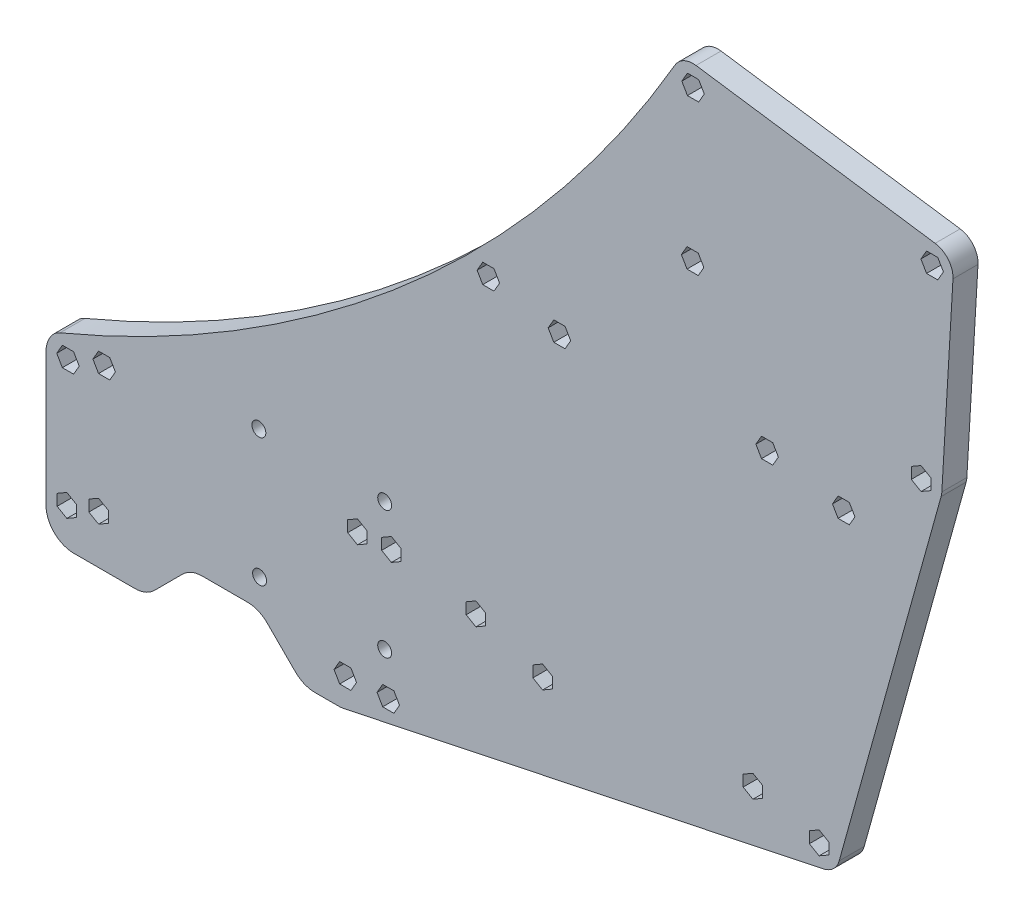
SolidWorks part; units mm, degrees
ref_plane "Front Plane" through (0, 0, 0) normal (0, 0, 1) x (1, 0, 0)
ref_plane "Top Plane" through (0, 0, 0) normal (0, 1, 0) x (1, 0, 0)
ref_plane "Right Plane" through (0, 0, 0) normal (1, 0, 0) x (0, 0, -1)
sketch "Model" plane through (0, 0, 0) normal (0, 0, 1) x (1, 0, 0)
  line L0 (-211.7059, 139.5585) -> (211.7058, 139.5585)
  line L1 (211.7058, 139.5585) -> (122.9838, -139.5584)
  line L2 (122.9838, -139.5584) -> (-211.7059, -139.5584)
  line L3 (-211.7059, -139.5584) -> (-211.7059, 139.5585)
  line L4 (-183.9889, -135.0098) -> (-175.7383, -135.0098)
  line L5 (-175.7383, -135.0098) -> (-175.7383, -139.5584)
  line L6 (-175.7383, -139.5584) -> (-183.9889, -139.5584)
  line L7 (-183.9889, -139.5584) -> (-183.9889, -135.0098)
  line L8 (5.1137, -131.3253) -> (16.7271, -131.3253)
  line L9 (16.7271, -131.3253) -> (16.7271, -139.5584)
  line L10 (16.7271, -139.5584) -> (5.1137, -139.5584)
  line L11 (5.1137, -139.5584) -> (5.1137, -131.3253)
  line L12 (-120.7856, -123.5542) -> (-97.2926, -123.5542)
  line L13 (-97.2926, -123.5542) -> (-97.2926, -126.7942)
  line L14 (-97.2926, -126.7942) -> (-120.7856, -126.7942)
  line L15 (-120.7856, -126.7942) -> (-120.7856, -123.5542)
  line L16 (-130.4136, -13.1631) -> (-127.7548, -13.1631)
  line L17 (-127.7548, -13.1631) -> (-127.7548, -110.9397)
  line L18 (-127.7548, -110.9397) -> (-130.4136, -110.9397)
  line L19 (-130.4136, -110.9397) -> (-130.4136, -13.1631)
  spline S0 degree 3 poles (121.2808, 104.4697) (121.2808, 103.8066) (121.0175, 103.1708) (120.5486, 102.7019) knots 0 0 0 0 1 1 1 1
  spline S1 degree 3 poles (120.5486, 102.7019) (120.0798, 102.2331) (119.4439, 101.9697) (118.7809, 101.9697) knots 0 0 0 0 1 1 1 1
  spline S2 degree 3 poles (118.7809, 101.9697) (117.4002, 101.9697) (116.2809, 103.089) (116.2809, 104.4697) knots 0 0 0 0 1 1 1 1
  spline S3 degree 3 poles (116.2809, 104.4697) (116.2809, 105.8504) (117.4002, 106.9696) (118.7809, 106.9696) knots 0 0 0 0 1 1 1 1
  spline S4 degree 3 poles (118.7809, 106.9696) (119.4439, 106.9696) (120.0798, 106.7062) (120.5486, 106.2374) knots 0 0 0 0 1 1 1 1
  spline S5 degree 3 poles (120.5486, 106.2374) (121.0175, 105.7686) (121.2808, 105.1327) (121.2808, 104.4697) knots 0 0 0 0 1 1 1 1
  spline S6 degree 3 poles (117.2766, 36.0936) (117.2766, 34.7129) (116.1574, 33.5937) (114.7767, 33.5937) knots 0 0 0 0 1 1 1 1
  spline S7 degree 3 poles (114.7767, 33.5937) (113.396, 33.5937) (112.2767, 34.7129) (112.2767, 36.0936) knots 0 0 0 0 1 1 1 1
  spline S8 degree 3 poles (112.2767, 36.0936) (112.2767, 37.4743) (113.396, 38.5936) (114.7767, 38.5936) knots 0 0 0 0 1 1 1 1
  spline S9 degree 3 poles (114.7767, 38.5936) (116.1574, 38.5936) (117.2766, 37.4743) (117.2766, 36.0936) knots 0 0 0 0 1 1 1 1
  spline S10 degree 3 poles (61.9275, 17.0977) (61.9275, 15.717) (60.8082, 14.5977) (59.4275, 14.5977) knots 0 0 0 0 1 1 1 1
  spline S11 degree 3 poles (59.4275, 14.5977) (58.0468, 14.5977) (56.9275, 15.717) (56.9275, 17.0977) knots 0 0 0 0 1 1 1 1
  spline S12 degree 3 poles (56.9275, 17.0977) (56.9275, 18.4784) (58.0468, 19.5976) (59.4275, 19.5976) knots 0 0 0 0 1 1 1 1
  spline S13 degree 3 poles (59.4275, 19.5976) (60.8082, 19.5976) (61.9275, 18.4784) (61.9275, 17.0977) knots 0 0 0 0 1 1 1 1
  spline S14 degree 3 poles (35.1266, 62.7496) (35.1266, 61.3689) (34.0074, 60.2496) (32.6267, 60.2496) knots 0 0 0 0 1 1 1 1
  spline S15 degree 3 poles (32.6267, 60.2496) (31.246, 60.2496) (30.1267, 61.3689) (30.1267, 62.7496) knots 0 0 0 0 1 1 1 1
  spline S16 degree 3 poles (30.1267, 62.7496) (30.1267, 64.1303) (31.246, 65.2496) (32.6267, 65.2496) knots 0 0 0 0 1 1 1 1
  spline S17 degree 3 poles (32.6267, 65.2496) (34.0074, 65.2496) (35.1266, 64.1303) (35.1266, 62.7496) knots 0 0 0 0 1 1 1 1
  spline S18 degree 3 poles (35.2798, 116.8664) (35.2798, 115.4857) (34.1605, 114.3664) (32.7798, 114.3664) knots 0 0 0 0 1 1 1 1
  spline S19 degree 3 poles (32.7798, 114.3664) (31.3991, 114.3664) (30.2798, 115.4857) (30.2798, 116.8664) knots 0 0 0 0 1 1 1 1
  spline S20 degree 3 poles (30.2798, 116.8664) (30.2798, 117.5294) (30.5432, 118.1653) (31.0121, 118.6341) knots 0 0 0 0 1 1 1 1
  spline S21 degree 3 poles (31.0121, 118.6341) (31.4809, 119.103) (32.1168, 119.3664) (32.7798, 119.3664) knots 0 0 0 0 1 1 1 1
  spline S22 degree 3 poles (32.7798, 119.3664) (33.4428, 119.3664) (34.0787, 119.103) (34.5475, 118.6341) knots 0 0 0 0 1 1 1 1
  spline S23 degree 3 poles (34.5475, 118.6341) (35.0164, 118.1653) (35.2798, 117.5294) (35.2798, 116.8664) knots 0 0 0 0 1 1 1 1
  spline S24 degree 3 poles (56.804, -89.9943) (56.804, -91.375) (55.6847, -92.4943) (54.304, -92.4943) knots 0 0 0 0 1 1 1 1
  spline S25 degree 3 poles (54.304, -92.4943) (52.9233, -92.4943) (51.804, -91.375) (51.804, -89.9943) knots 0 0 0 0 1 1 1 1
  spline S26 degree 3 poles (51.804, -89.9943) (51.804, -88.6136) (52.9233, -87.4943) (54.304, -87.4943) knots 0 0 0 0 1 1 1 1
  spline S27 degree 3 poles (54.304, -87.4943) (55.6847, -87.4943) (56.804, -88.6136) (56.804, -89.9943) knots 0 0 0 0 1 1 1 1
  spline S28 degree 3 poles (80.6115, -95.7304) (80.6115, -97.1111) (79.4922, -98.2304) (78.1115, -98.2304) knots 0 0 0 0 1 1 1 1
  spline S29 degree 3 poles (78.1115, -98.2304) (76.7308, -98.2304) (75.6115, -97.1111) (75.6115, -95.7304) knots 0 0 0 0 1 1 1 1
  spline S30 degree 3 poles (75.6115, -95.7304) (75.6115, -94.3497) (76.7308, -93.2304) (78.1115, -93.2304) knots 0 0 0 0 1 1 1 1
  spline S31 degree 3 poles (78.1115, -93.2304) (79.4922, -93.2304) (80.6115, -94.3497) (80.6115, -95.7304) knots 0 0 0 0 1 1 1 1
  spline S32 degree 3 poles (-189.541, -80.3042) (-189.541, -81.6849) (-190.6603, -82.8042) (-192.041, -82.8042) knots 0 0 0 0 1 1 1 1
  spline S33 degree 3 poles (-192.041, -82.8042) (-193.4217, -82.8042) (-194.5409, -81.6849) (-194.5409, -80.3042) knots 0 0 0 0 1 1 1 1
  spline S34 degree 3 poles (-194.5409, -80.3042) (-194.5409, -78.9235) (-193.4217, -77.8043) (-192.041, -77.8043) knots 0 0 0 0 1 1 1 1
  spline S35 degree 3 poles (-192.041, -77.8043) (-190.6603, -77.8043) (-189.541, -78.9235) (-189.541, -80.3042) knots 0 0 0 0 1 1 1 1
  spline S36 degree 3 poles (-85.4284, -81.8636) (-85.4284, -82.5266) (-85.6918, -83.1625) (-86.1606, -83.6313) knots 0 0 0 0 1 1 1 1
  spline S37 degree 3 poles (-86.1606, -83.6313) (-86.6295, -84.1001) (-87.2654, -84.3635) (-87.9284, -84.3635) knots 0 0 0 0 1 1 1 1
  spline S38 degree 3 poles (-87.9284, -84.3635) (-88.5914, -84.3635) (-89.2273, -84.1001) (-89.6961, -83.6313) knots 0 0 0 0 1 1 1 1
  spline S39 degree 3 poles (-89.6961, -83.6313) (-90.165, -83.1625) (-90.4284, -82.5266) (-90.4284, -81.8636) knots 0 0 0 0 1 1 1 1
  spline S40 degree 3 poles (-90.4284, -81.8636) (-90.4284, -80.4829) (-89.3091, -79.3636) (-87.9284, -79.3636) knots 0 0 0 0 1 1 1 1
  spline S41 degree 3 poles (-87.9284, -79.3636) (-86.5477, -79.3636) (-85.4284, -80.4829) (-85.4284, -81.8636) knots 0 0 0 0 1 1 1 1
  spline S42 degree 3 poles (-73.2184, -81.251) (-73.2184, -82.6317) (-74.3377, -83.7509) (-75.7183, -83.7509) knots 0 0 0 0 1 1 1 1
  spline S43 degree 3 poles (-75.7183, -83.7509) (-76.3814, -83.7509) (-77.0173, -83.4875) (-77.4861, -83.0187) knots 0 0 0 0 1 1 1 1
  spline S44 degree 3 poles (-77.4861, -83.0187) (-77.9549, -82.5499) (-78.2183, -81.914) (-78.2183, -81.251) knots 0 0 0 0 1 1 1 1
  spline S45 degree 3 poles (-78.2183, -81.251) (-78.2183, -80.5879) (-77.9549, -79.9521) (-77.4861, -79.4832) knots 0 0 0 0 1 1 1 1
  spline S46 degree 3 poles (-77.4861, -79.4832) (-77.0173, -79.0144) (-76.3814, -78.751) (-75.7183, -78.751) knots 0 0 0 0 1 1 1 1
  spline S47 degree 3 poles (-75.7183, -78.751) (-74.3377, -78.751) (-73.2184, -79.8703) (-73.2184, -81.251) knots 0 0 0 0 1 1 1 1
  spline S48 degree 3 poles (-42.8255, -86.1238) (-42.8255, -86.7869) (-43.0889, -87.4228) (-43.5578, -87.8916) knots 0 0 0 0 1 1 1 1
  spline S49 degree 3 poles (-43.5578, -87.8916) (-44.0266, -88.3604) (-44.6625, -88.6238) (-45.3255, -88.6238) knots 0 0 0 0 1 1 1 1
  spline S50 degree 3 poles (-45.3255, -88.6238) (-45.9885, -88.6238) (-46.6244, -88.3604) (-47.0932, -87.8916) knots 0 0 0 0 1 1 1 1
  spline S51 degree 3 poles (-47.0932, -87.8916) (-47.5621, -87.4228) (-47.8255, -86.7869) (-47.8255, -86.1238) knots 0 0 0 0 1 1 1 1
  spline S52 degree 3 poles (-47.8255, -86.1238) (-47.8255, -84.7432) (-46.7062, -83.6239) (-45.3255, -83.6239) knots 0 0 0 0 1 1 1 1
  spline S53 degree 3 poles (-45.3255, -83.6239) (-43.9448, -83.6239) (-42.8255, -84.7432) (-42.8255, -86.1238) knots 0 0 0 0 1 1 1 1
  spline S54 degree 3 poles (-18.8231, -93.7812) (-18.8231, -95.1619) (-19.9424, -96.2812) (-21.3231, -96.2812) knots 0 0 0 0 1 1 1 1
  spline S55 degree 3 poles (-21.3231, -96.2812) (-22.7038, -96.2812) (-23.823, -95.1619) (-23.823, -93.7812) knots 0 0 0 0 1 1 1 1
  spline S56 degree 3 poles (-23.823, -93.7812) (-23.823, -92.4005) (-22.7038, -91.2813) (-21.3231, -91.2813) knots 0 0 0 0 1 1 1 1
  spline S57 degree 3 poles (-21.3231, -91.2813) (-19.9424, -91.2813) (-18.8231, -92.4005) (-18.8231, -93.7812) knots 0 0 0 0 1 1 1 1
  spline S58 degree 3 poles (-38.3425, 21.163) (-38.3425, 19.7824) (-39.4618, 18.6631) (-40.8425, 18.6631) knots 0 0 0 0 1 1 1 1
  spline S59 degree 3 poles (-40.8425, 18.6631) (-42.2231, 18.6631) (-43.3424, 19.7824) (-43.3424, 21.163) knots 0 0 0 0 1 1 1 1
  spline S60 degree 3 poles (-43.3424, 21.163) (-43.3424, 22.5437) (-42.2231, 23.663) (-40.8425, 23.663) knots 0 0 0 0 1 1 1 1
  spline S61 degree 3 poles (-40.8425, 23.663) (-39.4618, 23.663) (-38.3425, 22.5437) (-38.3425, 21.163) knots 0 0 0 0 1 1 1 1
  spline S62 degree 3 poles (-12.7807, 15.9839) (-12.7807, 14.6032) (-13.9, 13.4839) (-15.2807, 13.4839) knots 0 0 0 0 1 1 1 1
  spline S63 degree 3 poles (-15.2807, 13.4839) (-16.6614, 13.4839) (-17.7807, 14.6032) (-17.7807, 15.9839) knots 0 0 0 0 1 1 1 1
  spline S64 degree 3 poles (-17.7807, 15.9839) (-17.7807, 17.3646) (-16.6614, 18.4838) (-15.2807, 18.4838) knots 0 0 0 0 1 1 1 1
  spline S65 degree 3 poles (-15.2807, 18.4838) (-13.9, 18.4838) (-12.7807, 17.3646) (-12.7807, 15.9839) knots 0 0 0 0 1 1 1 1
  spline S66 degree 3 poles (-176.5282, -75.6233) (-176.5282, -76.2863) (-176.7916, -76.9222) (-177.2604, -77.391) knots 0 0 0 0 1 1 1 1
  spline S67 degree 3 poles (-177.2604, -77.391) (-177.7293, -77.8599) (-178.3651, -78.1233) (-179.0282, -78.1233) knots 0 0 0 0 1 1 1 1
  spline S68 degree 3 poles (-179.0282, -78.1233) (-179.6912, -78.1233) (-180.3271, -77.8599) (-180.7959, -77.391) knots 0 0 0 0 1 1 1 1
  spline S69 degree 3 poles (-180.7959, -77.391) (-181.2647, -76.9222) (-181.5281, -76.2863) (-181.5281, -75.6233) knots 0 0 0 0 1 1 1 1
  spline S70 degree 3 poles (-181.5281, -75.6233) (-181.5281, -74.2426) (-180.4089, -73.1233) (-179.0282, -73.1233) knots 0 0 0 0 1 1 1 1
  spline S71 degree 3 poles (-179.0282, -73.1233) (-177.6475, -73.1233) (-176.5282, -74.2426) (-176.5282, -75.6233) knots 0 0 0 0 1 1 1 1
  spline S72 degree 3 poles (-189.9448, -125.9005) (-189.9448, -127.2812) (-191.064, -128.4004) (-192.4447, -128.4004) knots 0 0 0 0 1 1 1 1
  spline S73 degree 3 poles (-192.4447, -128.4004) (-193.8254, -128.4004) (-194.9447, -127.2812) (-194.9447, -125.9005) knots 0 0 0 0 1 1 1 1
  spline S74 degree 3 poles (-194.9447, -125.9005) (-194.9447, -124.5198) (-193.8254, -123.4005) (-192.4447, -123.4005) knots 0 0 0 0 1 1 1 1
  spline S75 degree 3 poles (-192.4447, -123.4005) (-191.064, -123.4005) (-189.9448, -124.5198) (-189.9448, -125.9005) knots 0 0 0 0 1 1 1 1
  spline S76 degree 3 poles (-178.5283, -121.9882) (-178.5283, -123.3689) (-179.6475, -124.4882) (-181.0282, -124.4882) knots 0 0 0 0 1 1 1 1
  spline S77 degree 3 poles (-181.0282, -124.4882) (-181.6913, -124.4882) (-182.3271, -124.2248) (-182.796, -123.756) knots 0 0 0 0 1 1 1 1
  spline S78 degree 3 poles (-182.796, -123.756) (-183.2648, -123.2871) (-183.5282, -122.6513) (-183.5282, -121.9882) knots 0 0 0 0 1 1 1 1
  spline S79 degree 3 poles (-183.5282, -121.9882) (-183.5282, -121.3252) (-183.2648, -120.6893) (-182.796, -120.2205) knots 0 0 0 0 1 1 1 1
  spline S80 degree 3 poles (-182.796, -120.2205) (-182.3271, -119.7516) (-181.6913, -119.4882) (-181.0282, -119.4882) knots 0 0 0 0 1 1 1 1
  spline S81 degree 3 poles (-181.0282, -119.4882) (-180.3652, -119.4882) (-179.7293, -119.7516) (-179.2605, -120.2205) knots 0 0 0 0 1 1 1 1
  spline S82 degree 3 poles (-179.2605, -120.2205) (-178.7917, -120.6893) (-178.5283, -121.3252) (-178.5283, -121.9882) knots 0 0 0 0 1 1 1 1
  spline S83 degree 3 poles (-74.3322, -128.3369) (-74.3322, -129.7176) (-75.4514, -130.8369) (-76.8321, -130.8369) knots 0 0 0 0 1 1 1 1
  spline S84 degree 3 poles (-76.8321, -130.8369) (-77.4952, -130.8369) (-78.1311, -130.5735) (-78.5999, -130.1046) knots 0 0 0 0 1 1 1 1
  spline S85 degree 3 poles (-78.5999, -130.1046) (-79.0687, -129.6358) (-79.3321, -128.9999) (-79.3321, -128.3369) knots 0 0 0 0 1 1 1 1
  spline S86 degree 3 poles (-79.3321, -128.3369) (-79.3321, -127.6739) (-79.0687, -127.038) (-78.5999, -126.5692) knots 0 0 0 0 1 1 1 1
  spline S87 degree 3 poles (-78.5999, -126.5692) (-78.1311, -126.1003) (-77.4952, -125.8369) (-76.8321, -125.8369) knots 0 0 0 0 1 1 1 1
  spline S88 degree 3 poles (-76.8321, -125.8369) (-75.4514, -125.8369) (-74.3322, -126.9562) (-74.3322, -128.3369) knots 0 0 0 0 1 1 1 1
  spline S89 degree 3 poles (-89.8001, -128.9495) (-89.8001, -129.6125) (-90.0635, -130.2484) (-90.5323, -130.7172) knots 0 0 0 0 1 1 1 1
  spline S90 degree 3 poles (-90.5323, -130.7172) (-91.0012, -131.1861) (-91.637, -131.4494) (-92.3001, -131.4494) knots 0 0 0 0 1 1 1 1
  spline S91 degree 3 poles (-92.3001, -131.4494) (-93.6808, -131.4494) (-94.8, -130.3302) (-94.8, -128.9495) knots 0 0 0 0 1 1 1 1
  spline S92 degree 3 poles (-94.8, -128.9495) (-94.8, -127.5688) (-93.6808, -126.4495) (-92.3001, -126.4495) knots 0 0 0 0 1 1 1 1
  spline S93 degree 3 poles (-92.3001, -126.4495) (-91.637, -126.4495) (-91.0012, -126.7129) (-90.5323, -127.1817) knots 0 0 0 0 1 1 1 1
  spline S94 degree 3 poles (-90.5323, -127.1817) (-90.0635, -127.6506) (-89.8001, -128.2864) (-89.8001, -128.9495) knots 0 0 0 0 1 1 1 1
  spline S95 degree 3 poles (89.4662, 12.2666) (89.4662, 10.8859) (88.3469, 9.7666) (86.9662, 9.7666) knots 0 0 0 0 1 1 1 1
  spline S96 degree 3 poles (86.9662, 9.7666) (85.5855, 9.7666) (84.4663, 10.8859) (84.4663, 12.2666) knots 0 0 0 0 1 1 1 1
  spline S97 degree 3 poles (84.4663, 12.2666) (84.4663, 13.6472) (85.5855, 14.7665) (86.9662, 14.7665) knots 0 0 0 0 1 1 1 1
  spline S98 degree 3 poles (86.9662, 14.7665) (88.3469, 14.7665) (89.4662, 13.6472) (89.4662, 12.2666) knots 0 0 0 0 1 1 1 1
sketch "Sketch2" plane through (0, 0, 0) normal (0, 0, 1) x (1, 0, 0)
  line L0 (-211.7059, -139.5584) -> (122.9838, -139.5584)
  line L18 (-211.7059, -139.5584) -> (-211.7059, 139.5585)
  line L19 (-211.7059, 139.5585) -> (211.7058, 139.5585)
  line L20 (211.7058, 139.5585) -> (122.9838, -139.5584)
  circle A0 centre (-192.4447, -125.9005) radius 2.5
  circle A1 centre (-181.0282, -121.9882) radius 2.5
  circle A2 centre (-192.041, -80.3042) radius 2.5
  circle A3 centre (-179.0282, -75.6233) radius 2.5
  circle A4 centre (-92.3001, -128.9495) radius 2.5
  circle A5 centre (-76.8321, -128.3369) radius 2.5
  circle A6 centre (-87.9284, -81.8636) radius 2.5
  circle A7 centre (-75.7183, -81.251) radius 2.5
  circle A8 centre (-45.3255, -86.1239) radius 2.5
  circle A9 centre (-21.3231, -93.7812) radius 2.5
  circle A10 centre (54.304, -89.9943) radius 2.5
  circle A11 centre (78.1115, -95.7304) radius 2.5
  circle A12 centre (114.7767, 36.0936) radius 2.5
  circle A13 centre (86.9662, 12.2666) radius 2.5
  circle A14 centre (59.4275, 17.0977) radius 2.5
  circle A15 centre (-40.8425, 21.163) radius 2.5
  circle A16 centre (-15.2807, 15.9839) radius 2.5
  circle A17 centre (32.6267, 62.7496) radius 2.5
  circle A18 centre (118.7809, 104.4697) radius 2.5
  circle A19 centre (32.7798, 116.8664) radius 2.5
extrude "Boss-Extrude1" add sketch "Sketch2" along normal blind 9
sketch "Sketch3" plane through (0, 0, 9) normal (0, 0, 1) x (1, 0, 0)
  line L0 (73.706, -139.5584) -> (151.3388, 139.5585)
  line L1 (-211.7059, -139.5584) -> (122.9838, -139.5584) construction
  line L2 (-211.7059, 139.5585) -> (211.7058, 139.5585) construction
  line L3 (-199.9447, 139.5585) -> (-199.9447, -139.5584)
  line L4 (-211.7059, -87.5749) -> (47.2794, 139.5585)
  line L5 (-211.7059, -139.5584) -> (-211.7059, 139.5585) construction
  line L6 (-211.7059, 124.3664) -> (206.8768, 124.3664)
  line L7 (211.7058, 139.5585) -> (122.9838, -139.5584) construction
  line L9 (211.7058, 139.5585) -> (-211.7059, 139.5585)
  line L10 (211.7058, 139.5585) -> (211.7058, -139.5584)
  line L11 (211.7058, -139.5584) -> (-211.7059, -139.5584)
  line L12 (-211.7059, 139.5585) -> (-211.7059, -139.5584)
  circle A0 centre (114.7767, 36.0936) radius 7.5
  circle A1 centre (78.1115, -95.7304) radius 7.5
  circle A2 centre (-192.4447, -125.9005) radius 7.5
  circle A3 centre (-192.041, -80.3042) radius 7.5
  circle A4 centre (32.7798, 116.8664) radius 7.5
  circle A5 centre (114.7767, 36.0936) radius 2.5 construction
  circle A6 centre (118.7809, 104.4697) radius 7.5
  line M29 (122.9838, -139.5584) -> (211.7058, 139.5585)
  line M30 (211.7058, 139.5585) -> (-211.7059, 139.5585)
  line M31 (-211.7059, 139.5585) -> (-211.7059, -139.5584)
  line M32 (-211.7059, -139.5584) -> (122.9838, -139.5584)
  dimension "D1" = 15
extrude "Cut-Extrude1" cut sketch "Sketch3" against normal blind 10 contours L6 L4 L3 M31 | L4 L3 M31 M32 | L6 L0 M32 M29 | L6 L3 L4 | L6 L3 M31 M30 | L3 L6 L4 M30 | L4 L6 L0 M30 | L0 L6 M29 M30 | L12 L11 L10 L9
sketch "Sketch4" plane through (0, 0, 9) normal (0, 0, 1) x (1, 0, 0)
  line L5 (-163.8851, -139.5584) -> (-147.8809, -123.5542)
  line L6 (-199.9447, -139.5584) -> (73.706, -139.5584) construction
  line L7 (-147.8809, -123.5542) -> (-123.3337, -123.5542)
  line L8 (-123.3337, -123.5542) -> (-107.3295, -139.5584)
  line L9 (-107.3295, -139.5584) -> (-163.8851, -139.5584)
  line L10 (-155.883, -131.5563) -> (-115.3316, -131.5563) construction
  line L11 (-135.6073, -123.5542) -> (-135.6073, -131.5563) construction
  line L12 (-128.1309, -123.5542) -> (-73.1309, -123.5542) construction
  line L13 (-147.8809, -91.0542) -> (-123.3337, -91.0542) construction
  line L14 (-147.8809, -85.5542) -> (-147.8809, -96.5542) construction
  line L15 (-123.3337, -72.156) -> (-123.3337, -109.9525) construction
  line L16 (-135.6073, -123.5542) -> (-135.6073, -91.0542) construction
  line L17 (-147.8809, -117.5859) -> (-147.8809, -123.5542) construction
  dimension "D1" = 45
extrude "Cut-Extrude2" cut sketch "Sketch4" against normal through all
sketch "Sketch5" plane through (0, 0, 9) normal (0, 0, 1) x (1, 0, 0)
  line L0 (-120.6309, -113.5542) -> (-125.6309, -113.5542) construction
  line L1 (-120.6309, -117.5542) -> (-120.6309, -109.5542) construction
  line L3 (-123.3809, -117.5859) -> (-123.3809, -64.5226) construction
  line L4 (-75.6309, -67.5542) -> (-80.6309, -67.5542) construction
  line L5 (-75.6309, -72.0542) -> (-75.6309, -63.0542) construction
  line L6 (-80.6309, -63.0542) -> (-80.6309, -72.0542) construction
  line L7 (-78.1309, -67.5542) -> (-123.3809, -67.5542) construction
  line L8 (-78.1309, -113.5542) -> (-78.1309, -67.5542) construction
  line L9 (-123.1309, -113.5542) -> (-78.1309, -113.5542) construction
  circle A0 centre (-123.1309, -113.5542) radius 2.5
  circle A1 centre (-78.1309, -113.5542) radius 2.5
  circle A2 centre (-123.3809, -67.5542) radius 2.5
  circle A3 centre (-78.1309, -67.5542) radius 2.5
  dimension "D1" = 5
extrude "Cut-Extrude3" cut sketch "Sketch5" against normal through all
sketch "Sketch6" plane through (0, 0, 9) normal (0, 0, 1) x (1, 0, 0)
  line L0 (-199.9447, -77.2602) -> (-199.9447, -139.5584) construction
  line L1 (-194.9336, -73.3845) -> (-199.9447, -73.3845)
  line L2 (-199.9447, -139.5584) -> (147.1133, -139.5584)
  line L3 (-199.9447, -139.5584) -> (-199.9447, 124.3664)
  line L4 (-199.9447, 124.3664) -> (147.1133, 124.3664)
  line L5 (147.1133, -139.5584) -> (147.1133, 124.3664)
  line L6 (26.2967, 120.6372) -> (26.2967, 124.3664)
  line L7 (33.8498, 124.2897) -> (119.8509, 111.8929)
  line L8 (126.2681, 104.0312) -> (122.2638, 35.6552)
  line L9 (122.2638, 35.6552) -> (147.1133, 35.6552)
  line L10 (79.656, -103.0696) -> (-93.736, -139.5584)
  line L11 (79.656, -103.0696) -> (147.1133, -103.0696)
  circle A0 centre (-192.041, -80.3042) radius 7.5
  circle A1 centre (-40.8425, 21.163) radius 7.5
  circle A3 centre (114.7767, 36.0936) radius 7.5
  circle A4 centre (32.7798, 116.8664) radius 7.5
  circle A5 centre (118.7809, 104.4697) radius 7.5
  circle A6 centre (78.1115, -95.7304) radius 7.5
  circle A7 centre (-76.8321, -128.3369) radius 7.5
  circle A8 centre (-192.4447, -125.9005) radius 7.5
  circle A9 centre (-179.0282, -75.6233) radius 7.5
  arc A10 (-194.9336, -73.3845) -> (26.2967, 120.6372) centre (-373.1679, 352.9825) ccw
  line M19 (73.706, -139.5584) -> (147.1133, 124.3664)
  line M20 (147.1133, 124.3664) -> (29.9569, 124.3664)
  line M21 (29.9569, 124.3664) -> (-199.9447, -77.2602)
extrude "Cut-Extrude5" cut sketch "Sketch6" against normal blind 10 contours L1 A10 L6 M21 | L9 L5 M19 | L11 L10 L2 M19 | A6 L11 M19 | A0 L1 M21 | L6 L4 M21 | A4 L6 M21 | A4 L4 M21 | A5 L8 L9 A4 L7 M19 M20 | A3 L9 M19
fillet "Fillet1" radius 10 7 edges at (-199.9447, -77.2602, 4.5) (-163.8851, -139.5584, 4.5) (-147.8809, -123.5542, 4.5) (-123.3337, -123.5542, 4.5) (-107.3295, -139.5584, 4.5) (-93.736, -139.5584, 4.5) (-199.9447, -139.5584, 4.5)
sketch "Sketch7" plane through (0, 0, 0) normal (0, 0, 1) x (1, 0, 0)
  line L1 (-190.0202, -83.8042) -> (-187.9995, -80.3042)
  line L2 (-187.9995, -80.3042) -> (-190.0202, -76.8042)
  line L3 (-190.0202, -76.8042) -> (-194.0617, -76.8042)
  line L4 (-194.0617, -76.8042) -> (-196.0824, -80.3042)
  line L5 (-196.0824, -80.3042) -> (-194.0617, -83.8042)
  line L6 (-194.0617, -83.8042) -> (-190.0202, -83.8042)
  line L7 (-181.0489, -79.1233) -> (-177.0074, -79.1233)
  line L8 (-177.0074, -79.1233) -> (-174.9867, -75.6233)
  line L9 (-174.9867, -75.6233) -> (-177.0074, -72.1233)
  line L10 (-177.0074, -72.1233) -> (-181.0489, -72.1233)
  line L11 (-181.0489, -72.1233) -> (-183.0696, -75.6233)
  line L12 (-183.0696, -75.6233) -> (-181.0489, -79.1233)
  line L13 (-192.4447, -129.9419) -> (-188.9447, -127.9212)
  line L14 (-188.9447, -127.9212) -> (-188.9447, -123.8798)
  line L15 (-188.9447, -123.8798) -> (-192.4447, -121.859)
  line L16 (-192.4447, -121.859) -> (-195.9447, -123.8798)
  line L17 (-195.9447, -123.8798) -> (-195.9447, -127.9212)
  line L18 (-195.9447, -127.9212) -> (-192.4447, -129.9419)
  line L19 (-177.5282, -124.0089) -> (-177.5282, -119.9675)
  line L20 (-177.5282, -119.9675) -> (-181.0282, -117.9468)
  line L21 (-181.0282, -117.9468) -> (-184.5282, -119.9675)
  line L22 (-184.5282, -119.9675) -> (-184.5282, -124.0089)
  line L23 (-184.5282, -124.0089) -> (-181.0282, -126.0297)
  line L24 (-181.0282, -126.0297) -> (-177.5282, -124.0089)
  line L25 (-96.3415, -128.9495) -> (-94.3208, -132.4495)
  line L26 (-94.3208, -132.4495) -> (-90.2793, -132.4495)
  line L27 (-90.2793, -132.4495) -> (-88.2586, -128.9495)
  line L28 (-88.2586, -128.9495) -> (-90.2793, -125.4495)
  line L29 (-90.2793, -125.4495) -> (-94.3208, -125.4495)
  line L30 (-94.3208, -125.4495) -> (-96.3415, -128.9495)
  line L31 (-80.8736, -128.3369) -> (-78.8529, -131.8369)
  line L32 (-78.8529, -131.8369) -> (-74.8114, -131.8369)
  line L33 (-74.8114, -131.8369) -> (-72.7907, -128.3369)
  line L34 (-72.7907, -128.3369) -> (-74.8114, -124.8369)
  line L35 (-74.8114, -124.8369) -> (-78.8529, -124.8369)
  line L36 (-78.8529, -124.8369) -> (-80.8736, -128.3369)
  line L37 (-91.4284, -83.8843) -> (-87.9284, -85.905)
  line L38 (-87.9284, -85.905) -> (-84.4284, -83.8843)
  line L39 (-84.4284, -83.8843) -> (-84.4284, -79.8428)
  line L40 (-84.4284, -79.8428) -> (-87.9284, -77.8221)
  line L41 (-87.9284, -77.8221) -> (-91.4284, -79.8428)
  line L42 (-91.4284, -79.8428) -> (-91.4284, -83.8843)
  line L43 (-72.2183, -83.2717) -> (-72.2183, -79.2302)
  line L44 (-72.2183, -79.2302) -> (-75.7183, -77.2095)
  line L45 (-75.7183, -77.2095) -> (-79.2183, -79.2302)
  line L46 (-79.2183, -79.2302) -> (-79.2183, -83.2717)
  line L47 (-79.2183, -83.2717) -> (-75.7183, -85.2924)
  line L48 (-75.7183, -85.2924) -> (-72.2183, -83.2717)
  line L49 (-45.3255, -90.1653) -> (-41.8255, -88.1446)
  line L50 (-41.8255, -88.1446) -> (-41.8255, -84.1031)
  line L51 (-41.8255, -84.1031) -> (-45.3255, -82.0824)
  line L52 (-45.3255, -82.0824) -> (-48.8255, -84.1031)
  line L53 (-48.8255, -84.1031) -> (-48.8255, -88.1446)
  line L54 (-48.8255, -88.1446) -> (-45.3255, -90.1653)
  line L55 (-21.3231, -97.8227) -> (-17.8231, -95.802)
  line L56 (-17.8231, -95.802) -> (-17.8231, -91.7605)
  line L57 (-17.8231, -91.7605) -> (-21.3231, -89.7398)
  line L58 (-21.3231, -89.7398) -> (-24.8231, -91.7605)
  line L59 (-24.8231, -91.7605) -> (-24.8231, -95.802)
  line L60 (-24.8231, -95.802) -> (-21.3231, -97.8227)
  line L61 (50.804, -92.015) -> (54.304, -94.0358)
  line L62 (54.304, -94.0358) -> (57.804, -92.015)
  line L63 (57.804, -92.015) -> (57.804, -87.9736)
  line L64 (57.804, -87.9736) -> (54.304, -85.9529)
  line L65 (54.304, -85.9529) -> (50.804, -87.9736)
  line L66 (50.804, -87.9736) -> (50.804, -92.015)
  line L67 (74.6115, -97.7511) -> (78.1115, -99.7718)
  line L68 (78.1115, -99.7718) -> (81.6115, -97.7511)
  line L69 (81.6115, -97.7511) -> (81.6115, -93.7097)
  line L70 (81.6115, -93.7097) -> (78.1115, -91.6889)
  line L71 (78.1115, -91.6889) -> (74.6115, -93.7097)
  line L72 (74.6115, -93.7097) -> (74.6115, -97.7511)
  line L73 (-38.8217, 17.663) -> (-36.801, 21.163)
  line L74 (-36.801, 21.163) -> (-38.8217, 24.663)
  line L75 (-38.8217, 24.663) -> (-42.8632, 24.663)
  line L76 (-42.8632, 24.663) -> (-44.8839, 21.163)
  line L77 (-44.8839, 21.163) -> (-42.8632, 17.663)
  line L78 (-42.8632, 17.663) -> (-38.8217, 17.663)
  line L79 (-11.2393, 15.9839) -> (-13.26, 19.4839)
  line L80 (-13.26, 19.4839) -> (-17.3014, 19.4839)
  line L81 (-17.3014, 19.4839) -> (-19.3222, 15.9839)
  line L82 (-19.3222, 15.9839) -> (-17.3014, 12.4839)
  line L83 (-17.3014, 12.4839) -> (-13.26, 12.4839)
  line L84 (-13.26, 12.4839) -> (-11.2393, 15.9839)
  line L85 (61.4482, 13.5977) -> (63.469, 17.0977)
  line L86 (63.469, 17.0977) -> (61.4482, 20.5977)
  line L87 (61.4482, 20.5977) -> (57.4068, 20.5977)
  line L88 (57.4068, 20.5977) -> (55.386, 17.0977)
  line L89 (55.386, 17.0977) -> (57.4068, 13.5977)
  line L90 (57.4068, 13.5977) -> (61.4482, 13.5977)
  line L91 (84.9455, 8.7666) -> (88.987, 8.7666)
  line L92 (88.987, 8.7666) -> (91.0077, 12.2666)
  line L93 (91.0077, 12.2666) -> (88.987, 15.7666)
  line L94 (88.987, 15.7666) -> (84.9455, 15.7666)
  line L95 (84.9455, 15.7666) -> (82.9248, 12.2666)
  line L96 (82.9248, 12.2666) -> (84.9455, 8.7666)
  line L97 (114.7767, 32.0522) -> (118.2767, 34.0729)
  line L98 (118.2767, 34.0729) -> (118.2767, 38.1144)
  line L99 (118.2767, 38.1144) -> (114.7767, 40.1351)
  line L100 (114.7767, 40.1351) -> (111.2767, 38.1144)
  line L101 (111.2767, 38.1144) -> (111.2767, 34.0729)
  line L102 (111.2767, 34.0729) -> (114.7767, 32.0522)
  line L103 (34.6474, 59.2496) -> (36.6681, 62.7496)
  line L104 (36.6681, 62.7496) -> (34.6474, 66.2496)
  line L105 (34.6474, 66.2496) -> (30.6059, 66.2496)
  line L106 (30.6059, 66.2496) -> (28.5852, 62.7496)
  line L107 (28.5852, 62.7496) -> (30.6059, 59.2496)
  line L108 (30.6059, 59.2496) -> (34.6474, 59.2496)
  line L109 (34.8005, 113.3664) -> (36.8213, 116.8664)
  line L110 (36.8213, 116.8664) -> (34.8005, 120.3664)
  line L111 (34.8005, 120.3664) -> (30.7591, 120.3664)
  line L112 (30.7591, 120.3664) -> (28.7383, 116.8664)
  line L113 (28.7383, 116.8664) -> (30.7591, 113.3664)
  line L114 (30.7591, 113.3664) -> (34.8005, 113.3664)
  line L115 (116.7602, 100.9697) -> (120.8016, 100.9697)
  line L116 (120.8016, 100.9697) -> (122.8223, 104.4697)
  line L117 (122.8223, 104.4697) -> (120.8016, 107.9697)
  line L118 (120.8016, 107.9697) -> (116.7602, 107.9697)
  line L119 (116.7602, 107.9697) -> (114.7394, 104.4697)
  line L120 (114.7394, 104.4697) -> (116.7602, 100.9697)
  circle A0 centre (-192.041, -80.3042) radius 3.5 construction
  circle A1 centre (-179.0282, -75.6233) radius 3.5 construction
  circle A2 centre (-192.4447, -125.9005) radius 3.5 construction
  circle A3 centre (-181.0282, -121.9882) radius 3.5 construction
  circle A4 centre (-92.3001, -128.9495) radius 3.5 construction
  circle A5 centre (-76.8321, -128.3369) radius 3.5 construction
  circle A6 centre (-87.9284, -81.8636) radius 3.5 construction
  circle A7 centre (-75.7183, -81.251) radius 3.5 construction
  circle A8 centre (-45.3255, -86.1239) radius 3.5 construction
  circle A9 centre (-21.3231, -93.7812) radius 3.5 construction
  circle A10 centre (54.304, -89.9943) radius 3.5 construction
  circle A11 centre (78.1115, -95.7304) radius 3.5 construction
  circle A12 centre (-40.8425, 21.163) radius 3.5 construction
  circle A13 centre (-15.2807, 15.9839) radius 3.5 construction
  circle A14 centre (59.4275, 17.0977) radius 3.5 construction
  circle A15 centre (86.9662, 12.2666) radius 3.5 construction
  circle A16 centre (114.7767, 36.0936) radius 3.5 construction
  circle A17 centre (32.6267, 62.7496) radius 3.5 construction
  circle A18 centre (32.7798, 116.8664) radius 3.5 construction
  circle A19 centre (118.7809, 104.4697) radius 3.5 construction
  point P172 (-177.0617, -72.0925)
  point P181 (81.573, -97.8163)
  point P182 (-44.8674, 21.5275)
  dimension "D1" = 7
extrude "Cut-Extrude6" cut sketch "Sketch7" along normal through all
